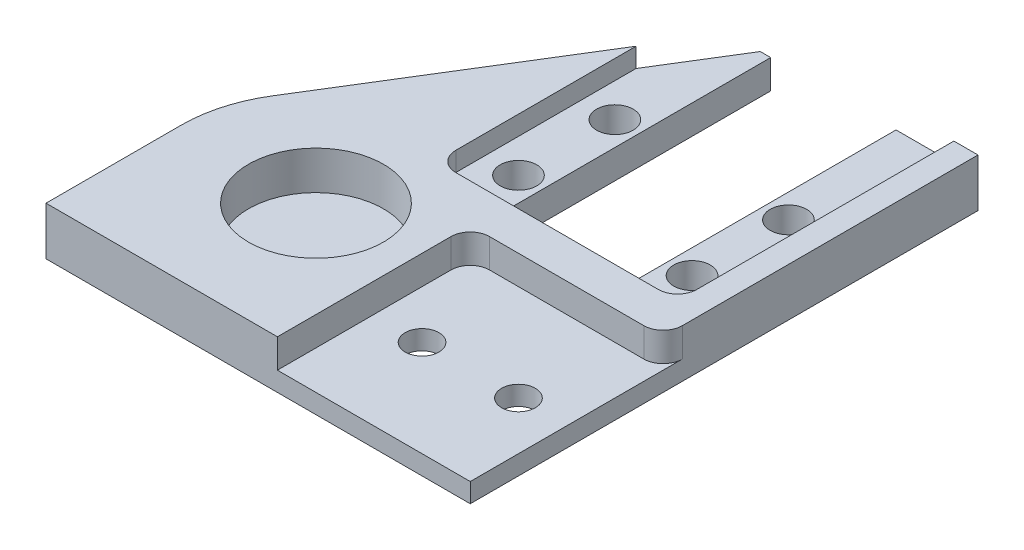
SolidWorks part; units mm, degrees
ref_plane "前视基准面" through (0, 0, 0) normal (0, 0, 1) x (1, 0, 0)
ref_plane "上视基准面" through (0, 0, 0) normal (0, 1, 0) x (1, 0, 0)
ref_plane "右视基准面" through (0, 0, 0) normal (1, 0, 0) x (0, 0, -1)
sketch "草图1" plane through (0, 0, 0) normal (0, 1, 0) x (1, 0, 0)
  line L1 (-17.5, -27.5) -> (17.5, -27.5)
  line L2 (-17.5, -27.5) -> (-17.5, 27.5)
  line L3 (-17.5, 27.5) -> (17.5, 27.5)
  line L4 (17.5, -27.5) -> (17.5, 27.5)
  line L5 (-17.5, -27.5) -> (17.5, 27.5) construction
  line L6 (-17.5, 27.5) -> (17.5, -27.5) construction
  point P0 (0, 0)
  dimension "D1" = 55
  dimension "D2" = 35
extrude "凸台-拉伸1" add sketch "草图1" along normal blind 1
sketch "草图2" plane through (0, 1, 0) normal (0, 1, 0) x (1, 0, 0)
  line L0 (-105.917, 0) -> (-62.25, 0) construction
  line L1 (106.75, 2.25) -> (121.75, 2.25)
  line L2 (-31.4474, 57.1013) -> (151.75, 26.6691)
  line L4 (124.0586, 2.6571) -> (154.0586, 13.5762)
  line L5 (-60.1618, 23.6059) -> (-42.6093, 52.0296)
  line L6 (121.75, 2.25) -> (121.75, 9) construction
  line L7 (121.75, -2.25) -> (121.75, -9) construction
  line L8 (-60.1618, -23.6059) -> (-42.6093, -52.0296)
  line L9 (124.0586, -2.6571) -> (154.0586, -13.5762)
  line L10 (121.75, -9) -> (128.5, -9)
  line L11 (-31.4474, -57.1013) -> (151.75, -26.6691)
  line L12 (106.75, -2.25) -> (121.75, -2.25)
  line L13 (-62.25, 16.25) -> (-62.25, -16.25)
  line L14 (106.75, 2.25) -> (106.75, -2.25)
  line L15 (106.75, 0) -> (124.0666, 0) construction
  arc A0 (-60.1618, 23.6059) -> (-62.25, 16.25) centre (-48.25, 16.25) ccw
  arc A1 (-31.4474, 57.1013) -> (-42.6093, 52.0296) centre (-33.25, 46.25) ccw
  arc A2 (121.75, 2.25) -> (124.0586, 2.6571) centre (121.75, 9) ccw
  arc A3 (154.0586, 13.5762) -> (151.75, 26.6691) centre (151.75, 19.9191) ccw
  arc A4 (154.0586, -13.5762) -> (151.75, -26.6691) centre (151.75, -19.9191) cw
  arc A5 (121.75, -2.25) -> (128.5, -9) centre (121.75, -9) cw
  arc A6 (-31.4474, -57.1013) -> (-42.6093, -52.0296) centre (-33.25, -46.25) cw
  arc A7 (-60.1618, -23.6059) -> (-62.25, -16.25) centre (-48.25, -16.25) cw
  line M10 (17.5, -27.5) -> (17.5, 27.5)
  line M11 (17.5, 27.5) -> (-17.5, 27.5)
  line M12 (-17.5, 27.5) -> (-17.5, -27.5)
  line M13 (-17.5, -27.5) -> (17.5, -27.5)
  dimension "D2" = 28
  dimension "D3" = 48.25
  dimension "D4" = 22
  dimension "D5" = 15
  dimension "D7" = 13.5
  dimension "D10" = 13.5
  dimension "D11" = 30
  dimension "D1" = 2.25
  dimension "D8" = 20
  dimension "D9" = 30
  dimension "D12" = 15
extrude "凸台-拉伸2" add sketch "草图2" along normal blind 3 contours A7 L8 A6 L11 A4 L9 A5 L12 L14 L1 A2 L4 A3 L2 A1 L5 A0 L13 | M13 M10 M11 M12 region at (37.3678, 1, 0) region at (0, 1, 0)
sketch "草图3" plane through (0, 4, 0) normal (0, 1, 0) x (1, 0, 0)
  circle A0 centre (-48.25, 16.25) radius 5
  circle A1 centre (-48.25, -16.25) radius 5
  circle A2 centre (-33.25, 46.25) radius 6.6982
  circle A3 centre (151.75, 19.9191) radius 2.5794
  circle A4 centre (121.75, 9) radius 2.5794
  circle A5 centre (121.75, -9) radius 2.5794
  circle A6 centre (151.75, -19.9191) radius 2.5794
  circle A7 centre (-33.25, -46.25) radius 6.6982
  dimension "D1" = 10
extrude "切除-拉伸1" cut sketch "草图3" against normal through all contours A0 | A1 region at (-48.25, 4, -16.25)
sketch "草图4" plane through (0, 4, 0) normal (0, 1, 0) x (1, 0, 0)
  circle A0 centre (-33.25, 46.25) radius 4
  circle A1 centre (-33.25, -46.25) radius 4
  dimension "D1" = 8
  dimension "D2" = 8
extrude "切除-拉伸2" cut sketch "草图4" against normal blind 2
sketch "草图5" plane through (0, 4, 0) normal (0, 1, 0) x (1, 0, 0)
  circle A0 centre (121.75, 9) radius 2
  circle A1 centre (121.75, -9) radius 2
  circle A2 centre (151.75, 19.9191) radius 2
  circle A3 centre (151.75, -19.9191) radius 2
  dimension "D1" = 4
extrude "切除-拉伸3" cut sketch "草图5" against normal blind 2
sketch "草图8" plane through (0, 1, 0) normal (0, -1, 0) x (1, 0, 0)
  line L1 (-39.75, -26.25) -> (-26.75, -26.25)
  line L2 (-39.75, -26.25) -> (-39.75, -66.25)
  line L3 (-39.75, -66.25) -> (-26.75, -66.25)
  line L4 (-26.75, -26.25) -> (-26.75, -66.25)
  line L5 (-39.75, -26.25) -> (-26.75, -66.25) construction
  line L6 (-39.75, -66.25) -> (-26.75, -26.25) construction
  line L16 (124.0586, 2.6571) -> (154.0586, 13.5762)
  line L17 (151.75, 26.6691) -> (-31.4474, 57.1013)
  line L18 (-42.6093, 52.0296) -> (-60.1618, 23.6059)
  line L19 (-62.25, 16.25) -> (-62.25, -16.25)
  line L20 (-60.1618, -23.6059) -> (-42.6093, -52.0296)
  line L21 (-31.4474, -57.1013) -> (151.75, -26.6691)
  line L22 (154.0586, -13.5762) -> (124.0586, -2.6571)
  line L23 (121.75, -2.25) -> (106.75, -2.25)
  line L24 (106.75, -2.25) -> (106.75, 2.25)
  line L25 (106.75, 2.25) -> (121.75, 2.25)
  line L26 (124.0586, 2.6571) -> (154.0586, 13.5762)
  line L27 (151.75, 26.6691) -> (-31.4474, 57.1013)
  line L28 (-42.6093, 52.0296) -> (-60.1618, 23.6059)
  line L31 (-31.4474, -57.1013) -> (151.75, -26.6691)
  line L32 (154.0586, -13.5762) -> (124.0586, -2.6571)
  line L33 (121.75, -2.25) -> (106.75, -2.25)
  line L34 (106.75, -2.25) -> (106.75, 2.25)
  line L35 (106.75, 2.25) -> (121.75, 2.25)
  arc A8 (154.0586, 13.5762) -> (151.75, 26.6691) centre (151.75, 19.9191) ccw
  arc A9 (-31.4474, 57.1013) -> (-42.6093, 52.0296) centre (-33.25, 46.25) ccw
  arc A10 (-60.1618, 23.6059) -> (-62.25, 16.25) centre (-48.25, 16.25) ccw
  arc A11 (-62.25, -16.25) -> (-60.1618, -23.6059) centre (-48.25, -16.25) ccw
  arc A12 (-42.6093, -52.0296) -> (-31.4474, -57.1013) centre (-33.25, -46.25) ccw
  arc A13 (151.75, -26.6691) -> (154.0586, -13.5762) centre (151.75, -19.9191) ccw
  arc A14 (124.0586, -2.6571) -> (121.75, -2.25) centre (121.75, -9) ccw
  arc A15 (121.75, 2.25) -> (124.0586, 2.6571) centre (121.75, 9) ccw
  arc A16 (154.0586, 13.5762) -> (151.75, 26.6691) centre (151.75, 19.9191) ccw
  arc A17 (-31.4474, 57.1013) -> (-42.6093, 52.0296) centre (-33.25, 46.25) ccw
  arc A18 (-60.1618, 23.6059) -> (-62.25, 16.25) centre (-48.25, 16.25) ccw
  arc A19 (-62.25, -16.25) -> (-60.1618, -23.6059) centre (-48.25, -16.25) ccw
  arc A20 (-42.6093, -52.0296) -> (-31.4474, -57.1013) centre (-33.25, -46.25) ccw
  arc A21 (151.75, -26.6691) -> (154.0586, -13.5762) centre (151.75, -19.9191) ccw
  arc A22 (124.0586, -2.6571) -> (121.75, -2.25) centre (121.75, -9) ccw
  arc A23 (121.75, 2.25) -> (124.0586, 2.6571) centre (121.75, 9) ccw
  point P0 (-33.25, -46.25)
  arc M32 (-42.6093, -52.0296) -> (-31.4474, -57.1013) centre (-33.25, -46.25) ccw
  line M33 (-31.4474, -57.1013) -> (151.75, -26.6691)
  dimension "D1" = 13
  dimension "D2" = 40
  dimension "D3" = 0
extrude "凸台-拉伸3" add sketch "草图8" along normal blind 7 contours L4 L1 L2 M32 M33 region at (-33.2258, 1, -41.4837)
mirror "镜向1" about plane through (0, 0, 0) normal (0, 0, 1) of "凸台-拉伸3"
sketch "草图9" plane through (0, -6, 0) normal (0, -1, 0) x (1, 0, 0)
  line L0 (-39.75, -26.25) -> (-26.75, -26.25) construction
  line L2 (-38.25, -53.75) -> (-38.25, -27.75)
  line L3 (-38.25, -27.75) -> (-28.25, -27.75)
  line L4 (-28.25, -53.75) -> (-28.25, -27.75)
  line L5 (-35.5448, -54.7408) -> (-28.25, -27.75) construction
  line L6 (-38.25, -27.75) -> (-31.223, -53.75) construction
  line L8 (-28.25, -53.75) -> (-38.25, -53.75)
  point P0 (-33.25, -46.25)
  dimension "D1" = 10
  dimension "D2" = 1.5
  dimension "D3" = 26
extrude "切除-拉伸4" cut sketch "草图9" against normal through all from offset 1.5 offset against normal yes
mirror "镜向2" about plane through (0, 0, 0) normal (0, 0, 1) of "切除-拉伸4"
sketch "草图10" plane through (0, 0, -53.75) normal (0, 0, 1) x (1, 0, 0)
  line L4 (-38.25, -4.5) -> (-28.25, -4.5)
  line L5 (-28.25, -4.5) -> (-28.25, 4)
  line L6 (-28.25, 4) -> (-38.25, 4)
  line L7 (-38.25, 4) -> (-38.25, -4.5)
  line L8 (-38.25, -4.5) -> (-28.25, -4.5)
  line L9 (-28.25, -4.5) -> (-28.25, 4)
  line L10 (-28.25, 4) -> (-38.25, 4)
  line L11 (-38.25, 4) -> (-38.25, -4.5)
  circle A0 centre (-33.25, -1.5) radius 1.5
  dimension "D2" = 3
  dimension "D3" = 3
  dimension "D1" = 0
extrude "切除-拉伸5" cut sketch "草图10" against normal through all contours A0 region at (-33.25, -1.5, -53.75)
mirror "镜向3" about plane through (0, 0, 0) normal (0, 0, 1) of "切除-拉伸5"
sketch "草图12" plane through (0, 4, 0) normal (0, 1, 0) x (1, 0, 0)
  line L3 (152.5362, 34.6481) -> (-30.1364, 64.9932)
  line L5 (-42.6093, 52.0296) -> (-60.1618, 23.6059) construction
  line L6 (124.0586, 2.6571) -> (154.0586, 13.5762) construction
  line L10 (154.0586, -13.5762) -> (124.0586, -2.6571)
  line L11 (121.75, -2.25) -> (106.75, -2.25)
  line L12 (106.75, -2.25) -> (106.75, 2.25)
  line L13 (106.75, 2.25) -> (121.75, 2.25)
  line L14 (124.0586, 2.6571) -> (154.0586, 13.5762)
  line L15 (151.75, 26.6691) -> (-31.4474, 57.1013)
  line L16 (-42.6093, 52.0296) -> (-60.1618, 23.6059)
  line L17 (-62.25, 16.25) -> (-62.25, -16.25)
  line L18 (-60.1618, -23.6059) -> (-42.6093, -52.0296)
  line L19 (-31.4474, -57.1013) -> (151.75, -26.6691)
  line L23 (-62.25, 2.25) -> (121.75, 2.25)
  line L24 (124.0586, 2.6571) -> (166.3826, 18.0617)
  line L26 (-34.4695, 65.2108) -> (-60.1618, 23.6059)
  line L27 (-62.25, 16.25) -> (-62.25, 2.25)
  line L30 (-49.416, 56.233) -> (-66.9685, 27.8093) construction
  line L31 (-70.25, 16.25) -> (-70.25, -5.75) construction
  line L32 (-70.25, -5.75) -> (121.75, -5.75) construction
  line L33 (126.7948, -4.8605) -> (156.7948, 6.0586) construction
  line L34 (151.75, 26.6691) -> (-31.4474, 57.1013) construction
  arc A1 (166.3826, 18.0617) -> (152.5362, 34.6481) centre (151.75, 19.9191) ccw
  arc A2 (-30.1364, 64.9932) -> (-34.4695, 65.2108) centre (-33.25, 46.25) ccw
  arc A4 (-30.1364, 64.9932) -> (-49.416, 56.233) centre (-33.25, 46.25) ccw construction
  arc A5 (156.7948, 6.0586) -> (152.5362, 34.6481) centre (151.75, 19.9191) ccw construction
  arc A8 (124.0586, -2.6571) -> (121.75, -2.25) centre (121.75, -9) ccw
  arc A9 (121.75, 2.25) -> (124.0586, 2.6571) centre (121.75, 9) ccw
  arc A10 (154.0586, 13.5762) -> (151.75, 26.6691) centre (151.75, 19.9191) ccw
  arc A11 (-31.4474, 57.1013) -> (-42.6093, 52.0296) centre (-33.25, 46.25) ccw
  arc A12 (-60.1618, 23.6059) -> (-62.25, 16.25) centre (-48.25, 16.25) ccw
  arc A13 (-62.25, -16.25) -> (-60.1618, -23.6059) centre (-48.25, -16.25) ccw
  arc A14 (-42.6093, -52.0296) -> (-31.4474, -57.1013) centre (-33.25, -46.25) ccw
  arc A15 (151.75, -26.6691) -> (154.0586, -13.5762) centre (151.75, -19.9191) ccw
  arc A17 (121.75, 2.25) -> (124.0586, 2.6571) centre (121.75, 9) ccw
  arc A20 (-60.1618, 23.6059) -> (-62.25, 16.25) centre (-48.25, 16.25) ccw
  arc A24 (-66.9685, 27.8093) -> (-70.25, 16.25) centre (-48.25, 16.25) ccw construction
  arc A25 (121.75, -5.75) -> (126.7948, -4.8605) centre (121.75, 9) ccw construction
  arc A26 (-31.4474, 57.1013) -> (-42.6093, 52.0296) centre (-33.25, 46.25) ccw construction
  arc A27 (154.0586, 13.5762) -> (151.75, 26.6691) centre (151.75, 19.9191) ccw construction
  dimension "D1" = 0
  dimension "D2" = 8
extrude "凸台-拉伸4" add sketch "草图12" along normal blind 3
sketch "草图13" plane through (0, 4, 0) normal (0, -1, 0) x (1, 0, 0)
  line L1 (-119.1699, 86.8947) -> (214.8426, 86.8947)
  line L2 (-119.1699, 86.8947) -> (-119.1699, -74.5615)
  line L3 (-119.1699, -74.5615) -> (214.8426, -74.5615)
  line L4 (214.8426, 86.8947) -> (214.8426, -74.5615)
  line L5 (-119.1699, 86.8947) -> (214.8426, -74.5615) construction
  line L6 (-119.1699, -74.5615) -> (214.8426, 86.8947) construction
  point P0 (47.8363, 6.1666)
extrude "切除-拉伸6" cut sketch "草图13" along normal blind 10
sketch "草图14" plane through (0, 4, 0) normal (0, -1, 0) x (1, 0, 0)
  circle A0 centre (151.75, -19.9191) radius 3.5
  circle A1 centre (121.75, -9) radius 3.5
  dimension "D2" = 7
  dimension "D3" = 7
extrude "切除-拉伸7" cut sketch "草图14" against normal through all from offset 0.5 offset against normal yes
sketch "草图15" plane through (0, 4, 0) normal (0, -1, 0) x (1, 0, 0)
  circle A0 centre (-48.25, -16.25) radius 5
  dimension "D1" = 10
extrude "切除-拉伸8" cut sketch "草图15" against normal through all
sketch "草图17" plane through (0, 4, 0) normal (0, -1, 0) x (1, 0, 0)
  line L0 (-30.6281, -62.0337) -> (152.2188, -31.6598)
  line L1 (-34.4695, -65.2108) -> (-36.5044, -61.9155)
  line L3 (166.3826, -18.0617) -> (163.0963, -16.8656)
  line L5 (166.3826, -18.0617) -> (124.0586, -2.6571)
  line L6 (121.75, -2.25) -> (-62.25, -2.25)
  line L7 (-62.25, -2.25) -> (-62.25, -16.25)
  line L8 (-60.1618, -23.6059) -> (-34.4695, -65.2108)
  line L9 (-30.1364, -64.9932) -> (152.5362, -34.6481)
  line L14 (-30.1364, -64.9932) -> (152.5362, -34.6481)
  arc A0 (-36.5044, -61.9155) -> (-30.6281, -62.0337) centre (-33.25, -46.25) ccw
  arc A1 (152.2188, -31.6598) -> (163.0963, -16.8656) centre (151.75, -19.9191) ccw
  arc A2 (-34.2769, -62.217) -> (-30.6281, -62.0337) centre (-33.25, -46.25) ccw construction
  arc A3 (152.2188, -31.6598) -> (163.4065, -18.4395) centre (151.75, -19.9191) ccw construction
  arc A4 (124.0586, -2.6571) -> (121.75, -2.25) centre (121.75, -9) ccw
  arc A5 (-62.25, -16.25) -> (-60.1618, -23.6059) centre (-48.25, -16.25) ccw
  arc A6 (-34.4695, -65.2108) -> (-30.1364, -64.9932) centre (-33.25, -46.25) ccw
  arc A7 (152.5362, -34.6481) -> (166.3826, -18.0617) centre (151.75, -19.9191) ccw
  arc A10 (-34.4695, -65.2108) -> (-30.1364, -64.9932) centre (-33.25, -46.25) ccw
  arc A11 (152.5362, -34.6481) -> (166.3826, -18.0617) centre (151.75, -19.9191) ccw
  dimension "D1" = 0
  dimension "D2" = 3
extrude "凸台-拉伸5" add sketch "草图17" against normal blind 16 from surface starting at face at (-48.25, 7, -21.25)
sketch "草图23" plane through (0, 4, 0) normal (0, -1, 0) x (1, 0, 0)
  line L2 (-39.75, -56.6598) -> (-39.75, -26.25)
  line L3 (-39.75, -26.25) -> (-26.75, -26.25)
  line L4 (-26.75, -64.4306) -> (-26.75, -26.25)
  line L5 (166.3826, -18.0617) -> (124.0586, -2.6571)
  line L6 (121.75, -2.25) -> (-62.25, -2.25)
  line L7 (-62.25, -2.25) -> (-62.25, -16.25)
  line L8 (-60.1618, -23.6059) -> (-34.4695, -65.2108)
  line L9 (-30.1364, -64.9932) -> (152.5362, -34.6481)
  line L13 (-39.75, -56.6598) -> (-34.4695, -65.2108)
  line L14 (-30.1364, -64.9932) -> (-26.75, -64.4306)
  line L15 (-37.7079, -59.9667) -> (-26.75, -26.25) construction
  line L16 (-39.75, -26.25) -> (-27.311, -64.5238) construction
  arc A4 (124.0586, -2.6571) -> (121.75, -2.25) centre (121.75, -9) ccw
  arc A5 (-62.25, -16.25) -> (-60.1618, -23.6059) centre (-48.25, -16.25) ccw
  arc A6 (-34.4695, -65.2108) -> (-30.1364, -64.9932) centre (-33.25, -46.25) ccw
  arc A7 (152.5362, -34.6481) -> (166.3826, -18.0617) centre (151.75, -19.9191) ccw
  arc A10 (-34.4695, -65.2108) -> (-30.1364, -64.9932) centre (-33.25, -46.25) ccw
  dimension "D3" = 13
  dimension "D1" = 0
extrude "凸台-拉伸7" add sketch "草图23" along normal blind 7
sketch "草图24" plane through (0, -3, 0) normal (0, -1, 0) x (1, 0, 0)
  line L0 (-38.25, -53.75) -> (-28.25, -53.75)
  line L2 (-38.25, -53.75) -> (-38.25, -27.75)
  line L3 (-38.25, -27.75) -> (-28.25, -27.75)
  line L4 (-28.25, -64.75) -> (-28.25, -64.6798)
  line L5 (-26.75, -64.4306) -> (-26.75, -26.25)
  line L6 (-26.75, -26.25) -> (-39.75, -26.25)
  line L7 (-39.75, -26.25) -> (-39.75, -56.6598)
  line L8 (-39.75, -56.6598) -> (-34.4695, -65.2108)
  line L9 (-30.1364, -64.9932) -> (-26.75, -64.4306)
  line L14 (-28.6727, -64.75) -> (-28.25, -64.6798)
  line L16 (-38.25, -27.75) -> (-31.223, -53.75) construction
  line L17 (-28.25, -53.75) -> (-28.25, -27.75)
  line L19 (-34.754, -64.75) -> (-34.4695, -65.2108)
  line L20 (-35.277, -53.75) -> (-28.25, -27.75) construction
  arc A1 (-34.4695, -65.2108) -> (-30.1364, -64.9932) centre (-33.25, -46.25) ccw
  dimension "D3" = 10
  dimension "D4" = 26
  dimension "D1" = 0
extrude "切除-拉伸11" cut sketch "草图24" against normal through all from offset 1.5 contours L0 L17 L3 L2 region at (-33.25, -3, -40.75) offset against normal yes
sketch "草图25" plane through (0, 0, -53.75) normal (0, 0, 1) x (1, 0, 0)
  line L4 (-28.25, 7) -> (-38.25, 7)
  line L5 (-38.25, 7) -> (-38.25, -1.5)
  line L6 (-38.25, -1.5) -> (-28.25, -1.5)
  line L7 (-28.25, -1.5) -> (-28.25, 7)
  line L8 (-28.25, 7) -> (-38.25, 7)
  line L9 (-38.25, 7) -> (-38.25, -1.5)
  line L10 (-38.25, -1.5) -> (-28.25, -1.5)
  line L11 (-28.25, -1.5) -> (-28.25, 7)
  circle A0 centre (-33.25, 1.5) radius 1.5
  dimension "D2" = 3
  dimension "D3" = 3
  dimension "D1" = 0
extrude "切除-拉伸12" cut sketch "草图25" against normal through all contours A0 region at (-33.25, 1.5, -53.75)
thread "螺纹线2" pitch 0.6 method cut profile "螺纹线轮廓2" start angle 0, offset 0, length 15, pitch 0.6, diameter 3
ref_plane "基准面2" through (-34.75, 1.5, -53.75) normal (0, -1, 0) x (-1, 0, 0)
sketch "螺纹线轮廓2" plane through (-34.75, 1.5, -53.75) normal (0, -1, 0) x (-1, 0, 0)
  line L0 (0, 0) -> (0, 0.6) construction
  line L1 (0, 0) -> (0.3248, 0.1875)
  line L2 (0.3248, 0.1875) -> (0.3248, 0.2625)
  line L3 (0.3248, 0.2625) -> (0, 0.45)
  line L4 (0.3248, 0.225) -> (0, 0.225) construction
  line L11 (0, 0) -> (0, 0.45)
  point P2 (0, 0)
  dimension "Pitch" = 0.6
  dimension "Profile_Angle" = 60
  dimension "Profile_Land" = 0.075
  dimension "Profile_Height" = 0.3248
sketch "草图26" plane through (0, -3, 0) normal (0, -1, 0) x (1, 0, 0)
  line L5 (-26.75, -64.4306) -> (-26.75, -26.25)
  line L6 (-26.75, -26.25) -> (-39.75, -26.25)
  line L7 (-39.75, -26.25) -> (-39.75, -56.6598)
  line L8 (-39.75, -56.6598) -> (-34.4695, -65.2108)
  line L9 (-30.1364, -64.9932) -> (-26.75, -64.4306)
  line L10 (-26.75, -64.4306) -> (-26.75, -26.25)
  line L11 (-26.75, -26.25) -> (-39.75, -26.25)
  line L12 (-39.75, -26.25) -> (-39.75, -56.6598)
  line L13 (-39.75, -56.6598) -> (-34.4695, -65.2108)
  line L14 (-30.1364, -64.9932) -> (-26.75, -64.4306)
  arc A1 (-34.4695, -65.2108) -> (-30.1364, -64.9932) centre (-33.25, -46.25) ccw
  arc A2 (-34.4695, -65.2108) -> (-30.1364, -64.9932) centre (-33.25, -46.25) ccw
  dimension "D1" = 0
extrude "切除-拉伸13" cut sketch "草图26" against normal through all
sketch "草图27" plane through (0, 4, 0) normal (0, -1, 0) x (1, 0, 0)
  line L0 (-45.75, -26.25) -> (-20.75, -26.25)
  line L1 (-20.75, -26.25) -> (-18.25, -26.25)
  line L2 (-18.25, -63.0186) -> (-18.25, -2.25)
  line L8 (-26.75, -26.25) -> (-26.75, -64.4306)
  line L9 (-26.75, -64.4306) -> (152.5362, -34.6481)
  line L10 (166.3826, -18.0617) -> (124.0586, -2.6571)
  line L11 (121.75, -2.25) -> (-62.25, -2.25)
  line L12 (-62.25, -2.25) -> (-62.25, -16.25)
  line L13 (-60.1618, -23.6059) -> (-39.75, -56.6598)
  line L14 (-39.75, -56.6598) -> (-39.75, -26.25)
  line L15 (-39.75, -26.25) -> (-26.75, -26.25)
  line L16 (-26.75, -26.25) -> (-26.75, -64.4306)
  line L17 (-26.75, -64.4306) -> (-18.25, -63.0186)
  line L19 (-18.25, -2.25) -> (-62.25, -2.25)
  line L20 (-62.25, -2.25) -> (-62.25, -16.25)
  line L21 (-60.1618, -23.6059) -> (-39.75, -56.6598)
  line L22 (-39.75, -56.6598) -> (-39.75, -26.25)
  line L23 (-39.75, -26.25) -> (-26.75, -26.25)
  circle A0 centre (-48.25, -16.25) radius 5 construction
  circle A1 centre (-48.25, -16.25) radius 5
  arc A3 (152.5362, -34.6481) -> (166.3826, -18.0617) centre (151.75, -19.9191) ccw
  arc A4 (124.0586, -2.6571) -> (121.75, -2.25) centre (121.75, -9) ccw
  arc A5 (-62.25, -16.25) -> (-60.1618, -23.6059) centre (-48.25, -16.25) ccw
  arc A8 (-62.25, -16.25) -> (-60.1618, -23.6059) centre (-48.25, -16.25) ccw
  point P12 (-33.25, -26.25)
  circle M14 centre (-48.25, -16.25) radius 5
  line M15 (-26.75, -26.25) -> (-26.75, -64.4306)
  line M16 (-26.75, -64.4306) -> (152.5362, -34.6481)
  line M20 (121.75, -2.25) -> (-62.25, -2.25)
  line M21 (-62.25, -2.25) -> (-62.25, -16.25)
  arc M22 (-62.25, -16.25) -> (-60.1618, -23.6059) centre (-48.25, -16.25) ccw
  line M23 (-60.1618, -23.6059) -> (-39.75, -56.6598)
  line M24 (-39.75, -56.6598) -> (-39.75, -26.25)
  line M25 (-39.75, -26.25) -> (-26.75, -26.25)
  dimension "D2" = 25
  dimension "D3" = 2.5
  dimension "D1" = 0
extrude "凸台-拉伸8" add sketch "草图27" along normal blind 2 contours L1 L2 L0 M20 M21 M22 M23 M24 M25 M14 | L2 L1 L0 M16 M15 region at (-40.852, 4, -19.0832) region at (-22.5267, 4, -44.9895)
sketch "草图28" plane through (0, 7, 0) normal (0, 1, 0) x (1, 0, 0)
  line L0 (-45.75, 26.25) -> (-20.75, 26.25)
  line L2 (-45.75, 26.25) -> (-45.75, 73.8905)
  line L3 (-20.75, 26.25) -> (-20.75, 73.8905)
  line L4 (-20.75, 73.8905) -> (-45.75, 73.8905)
  point P3 (-33.25, 26.25)
  dimension "D1" = 25
extrude "切除-拉伸14" cut sketch "草图28" along normal through all from offset 2 offset against normal yes
sketch "草图29" plane through (0, 7, 0) normal (0, 1, 0) x (1, 0, 0)
  circle A0 centre (-48.25, 16.25) radius 7
  dimension "D1" = 14
extrude "切除-拉伸15" cut sketch "草图29" against normal blind 4
sketch "草图31" plane through (0, 4, 0) normal (0, -1, 0) x (1, 0, 0)
  line L0 (-48.25, -16.25) -> (103.8912, -16.25)
  line L1 (1.75, -16.25) -> (5.75, -16.25) construction
  line L2 (1.75, -14.5) -> (5.75, -14.5)
  line L3 (1.75, -18) -> (5.75, -18)
  line L4 (41.75, -16.25) -> (45.75, -16.25) construction
  line L5 (41.75, -14.5) -> (45.75, -14.5)
  line L6 (41.75, -18) -> (45.75, -18)
  line L7 (81.75, -16.25) -> (85.75, -16.25) construction
  line L8 (81.75, -14.5) -> (85.75, -14.5)
  line L9 (81.75, -18) -> (85.75, -18)
  line L10 (1.75, -31.25) -> (1.75, -35.25) construction
  line L11 (3.5, -31.25) -> (3.5, -35.25)
  line L12 (0, -31.25) -> (0, -35.25)
  arc A0 (1.75, -14.5) -> (1.75, -18) centre (1.75, -16.25) ccw
  arc A1 (5.75, -18) -> (5.75, -14.5) centre (5.75, -16.25) ccw
  arc A2 (41.75, -14.5) -> (41.75, -18) centre (41.75, -16.25) ccw
  arc A3 (45.75, -18) -> (45.75, -14.5) centre (45.75, -16.25) ccw
  arc A4 (81.75, -14.5) -> (81.75, -18) centre (81.75, -16.25) ccw
  arc A5 (85.75, -18) -> (85.75, -14.5) centre (85.75, -16.25) ccw
  circle A6 centre (-48.25, -16.25) radius 5 construction
  arc A7 (3.5, -31.25) -> (0, -31.25) centre (1.75, -31.25) ccw
  arc A8 (0, -35.25) -> (3.5, -35.25) centre (1.75, -35.25) ccw
  point P5 (3.75, -16.25)
  point P10 (43.75, -16.25)
  point P17 (83.75, -16.25)
  point P28 (1.75, -33.25)
  dimension "D3" = 50
  dimension "D4" = 40
  dimension "D5" = 40
  dimension "D6" = 15
  dimension "D1" = 3.5
  dimension "D2" = 4
extrude "切除-拉伸16" cut sketch "草图31" against normal blind 10 contours L3 A1 L0 A0 | L0 A1 L2 A0 | L6 A3 L0 A2 | L0 A3 L5 A2 | L0 A5 L8 A4 | L9 A5 L0 A4 | L12 A8 L11 A7 region at (3.75, 4, -15.4289) region at (83.75, 4, -15.4289) region at (83.75, 4, -17.0711) region at (43.75, 4, -15.4289) region at (43.75, 4, -17.0711) region at (3.75, 4, -17.0711) region at (1.75, 4, -33.25)
sketch "草图32" plane through (0, 5, 0) normal (0, 1, 0) x (1, 0, 0)
  line L0 (-26.75, 26.25) -> (-20.75, 26.25)
  line L1 (-45.75, 26.25) -> (-39.75, 26.25)
  line L2 (-45.75, 26.25) -> (-20.75, 26.25) construction
  line L3 (-45.75, 26.25) -> (-39.75, 26.25) construction
  line L4 (-33.25, 26.25) -> (-33.25, 45.9067) construction
  circle A0 centre (-42.25, 31.25) radius 1.8968
  circle A1 centre (-24.25, 31.25) radius 1.8968
  circle A2 centre (-24.25, 41.25) radius 1.8968
  circle A3 centre (-42.25, 41.25) radius 1.8968
  dimension "D2" = 10
  dimension "D3" = 5
  dimension "D4" = 10
  dimension "D5" = 18
  dimension "D6" = 9
  dimension "D1" = 5
extrude "切除-拉伸17" cut sketch "草图32" against normal blind 10 contours A3 | A0 | A2 | A1 region at (-42.25, 5, -31.25) region at (-24.25, 5, -41.25) region at (-42.25, 5, -41.25)
sketch "草图33" plane through (0, 23, 0) normal (0, 1, 0) x (1, 0, 0)
  line L0 (-26.75, 56.321) -> (151.75, 26.6691)
  line L1 (124.0586, 2.6571) -> (163.0963, 16.8656) construction
  line L2 (154.0586, 13.5762) -> (163.0963, 16.8656)
  line L3 (-26.75, 64.4306) -> (-26.75, 26.25) construction
  line L4 (152.5362, 34.6481) -> (-20.75, 63.4339)
  line L5 (-20.75, 63.4339) -> (-20.75, 60.3928)
  line L6 (-20.75, 60.3928) -> (152.2188, 31.6598)
  line L7 (163.0963, 16.8656) -> (166.3826, 18.0617)
  line L8 (152.5362, 34.6481) -> (-20.75, 63.4339)
  line L11 (163.0963, 16.8656) -> (166.3826, 18.0617)
  line L12 (-26.75, 64.4306) -> (-26.75, 56.321)
  line L13 (-20.75, 63.4339) -> (-26.75, 64.4306) construction
  line L14 (-20.75, 63.4339) -> (-26.75, 64.4306)
  arc A0 (154.0586, 13.5762) -> (151.75, 26.6691) centre (151.75, 19.9191) ccw
  arc A2 (163.0963, 16.8656) -> (152.2188, 31.6598) centre (151.75, 19.9191) ccw
  arc A3 (166.3826, 18.0617) -> (152.5362, 34.6481) centre (151.75, 19.9191) ccw
  arc A5 (166.3826, 18.0617) -> (152.5362, 34.6481) centre (151.75, 19.9191) ccw
  dimension "D1" = 0
extrude "切除-拉伸18" cut sketch "草图33" along normal blind 2 from surface starting at face at (1.75, 4, -33.25)
sketch "草图34" plane through (0, 23, 0) normal (0, 1, 0) x (1, 0, 0)
  line L4 (152.5362, 34.6481) -> (-20.75, 63.4339)
  line L5 (-20.75, 63.4339) -> (-20.75, 60.3928)
  line L6 (-20.75, 60.3928) -> (152.2188, 31.6598)
  line L7 (163.0963, 16.8656) -> (166.3826, 18.0617)
  line L8 (152.5362, 34.6481) -> (-20.75, 63.4339)
  line L9 (-20.75, 63.4339) -> (-20.75, 60.3928)
  line L10 (-20.75, 60.3928) -> (152.2188, 31.6598)
  line L11 (163.0963, 16.8656) -> (166.3826, 18.0617)
  arc A2 (163.0963, 16.8656) -> (152.2188, 31.6598) centre (151.75, 19.9191) ccw
  arc A3 (166.3826, 18.0617) -> (152.5362, 34.6481) centre (151.75, 19.9191) ccw
  arc A4 (163.0963, 16.8656) -> (152.2188, 31.6598) centre (151.75, 19.9191) ccw
  arc A5 (166.3826, 18.0617) -> (152.5362, 34.6481) centre (151.75, 19.9191) ccw
  dimension "D1" = 0
extrude "切除-拉伸19" cut sketch "草图34" against normal through all
sketch "草图35" plane through (0, 6, 0) normal (0, -1, 0) x (1, 0, 0)
  line L0 (-20.75, -55.3243) -> (151.75, -26.6691) construction
  line L1 (-20.75, -55.3243) -> (151.75, -26.6691)
  line L2 (-20.75, -55.3243) -> (-34.502, -57.6087)
  line L3 (-34.502, -57.6087) -> (-32.1341, -71.8628)
  line L4 (-32.1341, -71.8628) -> (-8.5776, -67.9497)
  line L5 (-8.5776, -67.9497) -> (-10.9454, -53.6956)
  line M1 (-20.75, -60.3928) -> (152.2188, -31.6598)
  line M6 (-20.75, -55.3243) -> (-20.75, -60.3928)
extrude "切除-拉伸20" cut sketch "草图35" along normal through all contours L4 L5 L2 L3 M1 M6 | L5 L1 M1 M6 region at (-22.5812, 6, -63.7917) region at (-15.6401, 6, -57.0436)
sketch "草图36" plane through (0, 6, 0) normal (0, -1, 0) x (1, 0, 0)
  line L0 (-18.25, -54.909) -> (-18.25, -59.9775)
  line L1 (-20.75, -60.3928) -> (152.2188, -31.6598) construction
  line L2 (-18.25, -59.9775) -> (-20.75, -60.3928)
  line L3 (-20.75, -60.3928) -> (-20.75, -55.3243)
  line L4 (-20.75, -55.3243) -> (-18.25, -54.909)
extrude "切除-拉伸21" cut sketch "草图36" against normal through all
sketch "草图37" plane through (0, 6, 0) normal (0, -1, 0) x (1, 0, 0)
  line L1 (-18.25, -59.9775) -> (-18.25, -54.909) construction
  line L2 (-18.6597, -57.5113) -> (151.8091, -29.1935)
  line L3 (-18.25, -57.4432) -> (151.8091, -29.1935)
  line L4 (-18.25, -59.9775) -> (-18.25, -54.909)
  circle A0 centre (11.3445, -52.5271) radius 1
  circle A1 centre (50.8037, -45.9723) radius 1
  circle A2 centre (90.263, -39.4174) radius 1
  circle A3 centre (129.7223, -32.8625) radius 1
  dimension "D2" = 2
  dimension "D4" = 40
  dimension "D5" = 80
  dimension "D6" = 120
  dimension "D3" = 30
  dimension "D1" = 2.5
extrude "切除-拉伸22" cut sketch "草图37" against normal through all contours L3 A0 | L3 A0 | L3 A3 | L3 A3 | A1 | A2 region at (11.2749, 6, -52.1084) region at (129.6527, 6, -32.4439) region at (129.7918, 6, -33.2812) region at (11.414, 6, -52.9458)
sketch "草图39" plane through (0, 3, 0) normal (0, 1, 0) x (1, 0, 0)
  circle A0 centre (-48.25, 16.25) radius 5 construction
  circle A1 centre (-48.25, 16.25) radius 5
extrude "凸台-拉伸9" add sketch "草图39" against normal up to surface (1 mm away) up to face at (-42.25, 2, -33.1468)
sketch "草图40" plane through (-18.25, 0, 0) normal (-1, 0, 0) x (0, 0, 1)
  line L1 (-54.909, 7) -> (-57.3049, 7)
  line L2 (-54.909, 7) -> (-54.909, 1.313)
  line L3 (-54.909, 1.313) -> (-57.3049, 1.313)
  line L4 (-57.3049, 7) -> (-57.3049, 1.313)
extrude "切除-拉伸23" cut sketch "草图40" along normal through all
sketch "草图41" plane through (-18.25, 0, 0) normal (1, 0, 0) x (0, 0, -1)
  line L1 (-17.6532, 20.6801) -> (66.8295, 20.6801)
  line L2 (-17.6532, 20.6801) -> (-17.6532, -14.2717)
  line L3 (-17.6532, -14.2717) -> (66.8295, -14.2717)
  line L4 (66.8295, 20.6801) -> (66.8295, -14.2717)
extrude "切除-拉伸24" cut sketch "草图41" along normal through all
sketch "草图42" plane through (-18.25, 0, 0) normal (1, 0, 0) x (0, 0, -1)
  line L1 (2.25, 7) -> (22.25, 7)
  line L2 (2.25, 7) -> (2.25, 4)
  line L3 (2.25, 4) -> (22.25, 4)
  line L4 (22.25, 7) -> (22.25, 4)
  dimension "D1" = 20
  dimension "D2" = 3
extrude "切除-拉伸25" cut sketch "草图42" against normal blind 20
sketch "草图43" plane through (0, 4, 0) normal (0, 1, 0) x (1, 0, 0)
  line L0 (-18.25, 12.25) -> (-35.5907, 12.25)
  line L1 (-18.25, 2.25) -> (-18.25, 22.25) construction
  circle A0 centre (-23.25, 12.25) radius 1.75
  circle A1 centre (-33.25, 12.25) radius 1.75
  dimension "D1" = 3.5
  dimension "D2" = 3.5
  dimension "D3" = 5
  dimension "D4" = 10
extrude "切除-拉伸26" cut sketch "草图43" against normal blind 20 contours L0 A1 | L0 A1 | L0 A0 | A0 region at (-23.25, 4, -12.9927) region at (-33.25, 4, -11.5073) region at (-33.25, 4, -12.9927)
fillet "圆角1" radius 2 4 edges at (-20.75, 6, -26.25) (-26.75, 3.5, -26.25) (-39.75, 3.5, -26.25) (-45.75, 6, -26.25)
fillet "圆角2" radius 2 2 edges at (-18.25, 5.5, -22.25) (-38.25, 5.5, -22.25)
